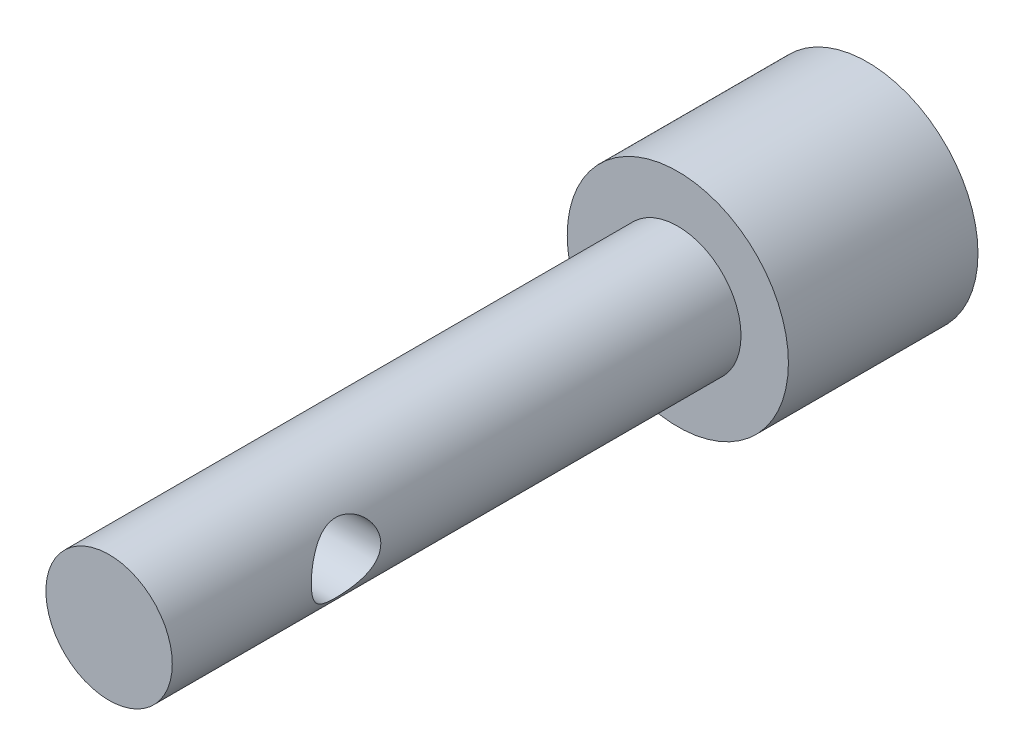
SolidWorks part; units mm, degrees
ref_plane "Płaszczyzna przednia" through (0, 0, 0) normal (0, 0, 1) x (1, 0, 0)
ref_plane "Płaszczyzna górna" through (0, 0, 0) normal (0, 1, 0) x (1, 0, 0)
ref_plane "Płaszczyzna prawa" through (0, 0, 0) normal (1, 0, 0) x (0, 0, -1)
sketch "Szkic1" plane through (0, 0, 0) normal (0, 0, 1) x (1, 0, 0)
  circle A0 centre (0, 0) radius 3.5
extrude "Dodanie-wyciągnięcie1" add sketch "Szkic1" along normal blind 6
sketch "Szkic2" plane through (0, 0, 6) normal (0, 0, 1) x (1, 0, 0)
  circle A0 centre (0, 0) radius 2
extrude "Dodanie-wyciągnięcie2" add sketch "Szkic2" along normal blind 18
ref_plane "Płaszczyzna1" through (-2, 0, 0) normal (-1, 0, 0) x (0, 0, 1)
sketch "Szkic3" plane through (-2, 0, 0) normal (-1, 0, 0) x (0, 0, 1)
  line L0 (6, -2) -> (6, 2) construction
  circle A0 centre (18.5, 0) radius 1.1
  dimension "12,5" = 12.5
extrude "Wytnij-wyciągnięcie1" cut sketch "Szkic3" against normal through all
sketch "Szkic4" plane through (0, 0, 0) normal (0, 0, -1) x (-1, 0, 0)
  circle A0 centre (0, 0) radius 2.3
  dimension "D1" = 4.6
extrude "Wytnij-wyciągnięcie2" cut sketch "Szkic4" against normal blind 3
